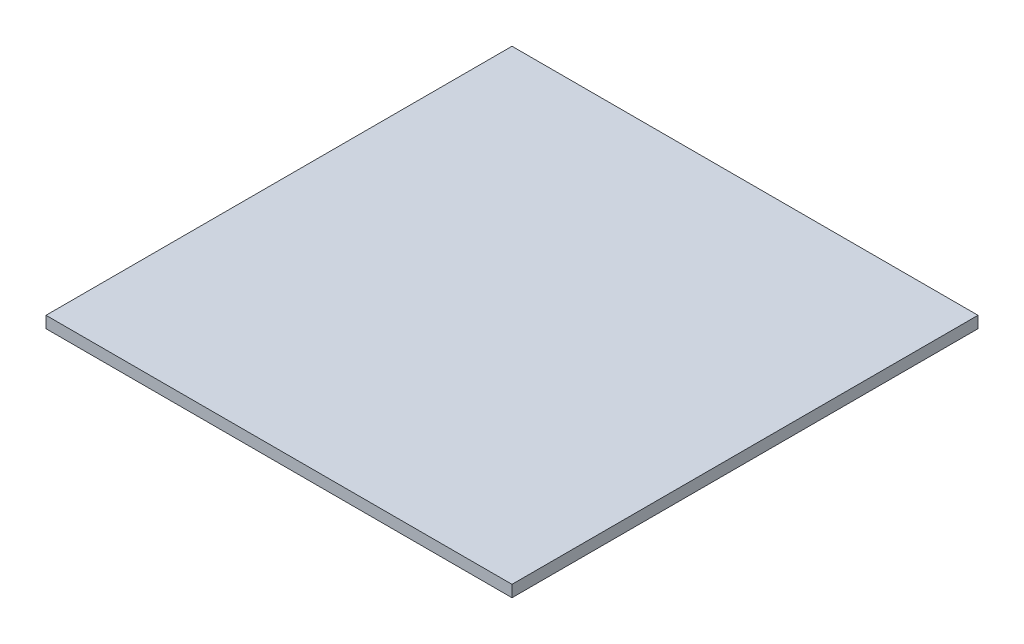
SolidWorks part; units mm, degrees
material "Vidrio"
ref_plane "Alzado" through (0, 0, 0) normal (0, 0, 1) x (1, 0, 0)
ref_plane "Planta" through (0, 0, 0) normal (0, 1, 0) x (1, 0, 0)
ref_plane "Vista lateral" through (0, 0, 0) normal (1, 0, 0) x (0, 0, -1)
sketch "Sketch1" plane through (0, 0, 0) normal (0, 1, 0) x (1, 0, 0)
  line L1 (-60, -60) -> (60, -60)
  line L2 (-60, -60) -> (-60, 60)
  line L3 (-60, 60) -> (60, 60)
  line L4 (60, -60) -> (60, 60)
  line L5 (-60, -60) -> (60, 60) construction
  line L6 (-60, 60) -> (60, -60) construction
  point P0 (0, 0)
  dimension "D1" = 120
  dimension "D2" = 120
extrude "Boss-Extrude1" add sketch "Sketch1" along normal blind 3
